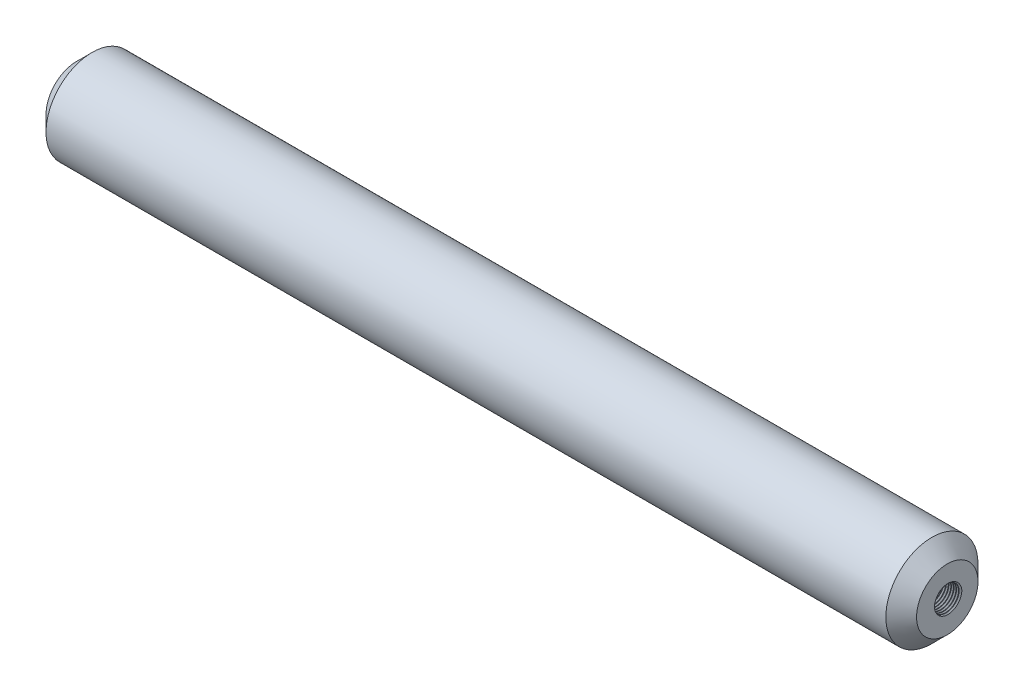
SolidWorks part; units mm, degrees
ref_plane "Front Plane" through (0, 0, 0) normal (0, 0, 1) x (1, 0, 0)
ref_plane "Top Plane" through (0, 0, 0) normal (0, 1, 0) x (1, 0, 0)
ref_plane "Right Plane" through (0, 0, 0) normal (1, 0, 0) x (0, 0, -1)
sketch "Sketch1" plane through (0, 0, 0) normal (1, 0, 0) x (0, 0, -1)
  circle A0 centre (0, 0) radius 9
  dimension "D1" = 18
extrude "Boss-Extrude1" add sketch "Sketch1" against normal blind 170
sketch "Sketch2" plane through (0, 0, 0) normal (1, 0, 0) x (0, 0, -1)
  circle A0 centre (0, 0) radius 2.5
  dimension "D1" = 5
extrude "Cut-Extrude1" cut sketch "Sketch2" against normal blind 24
sketch "Sketch3" plane through (-170, 0, 0) normal (-1, 0, 0) x (0, 0, 1)
  circle A0 centre (0, 0) radius 2.5
  dimension "D1" = 5
extrude "Cut-Extrude2" cut sketch "Sketch3" against normal blind 24
sketch "Sketch4" plane through (0, 0, 0) normal (1, 0, 0) x (0, 0, -1)
  circle A0 centre (0, 0) radius 2.5
  dimension "D1" = 5
curve "Helix/Spiral1" pitch 0.5 height 18 turns 36
sketch "Sketch5" plane through (0, 0, 0) normal (1, 0, 0) x (0, 0, -1)
  line L1 (2.5, 0) -> (0, 0) construction
  circle A0 centre (0, 0) radius 2.5 construction
sketch3d "3DSketch5"
  point P0 (0, 0, -2.5)
sketch3d "3DSketch6"
  line L0 (0.2, 0, -2.5) -> (-0.2, 0, -2.5)
  line L2 (0.2, 0, -2.5) -> (-0.0014, 0, -2.8472)
  line L3 (-0.0014, 0, -2.8472) -> (-0.2, 0, -2.5)
  point P11 (0, 0, -2.5)
  dimension "D1" = 0.4
  dimension "D2" = 0.4
sweep "Cut-Sweep5" cut profiles "3DSketch6" path "Helix/Spiral1"
sketch "Sketch8" plane through (-170, 0, 0) normal (-1, 0, 0) x (0, 0, 1)
  circle A0 centre (0, 0) radius 2.5
curve "Helix/Spiral3" pitch 0.5 height 18 turns 36
sketch "Sketch9" plane through (-170, 0, 0) normal (-1, 0, 0) x (0, 0, 1)
  line L0 (0, 0) -> (2.5, 0) construction
  circle A0 centre (0, 0) radius 2.5 construction
sketch3d "3DSketch7"
  point P0 (-170, 0, 2.5)
sketch3d "3DSketch8"
  line L0 (-169.8, 0, 2.5) -> (-170, 0, 2.8464)
  line L1 (-170.2, 0, 2.5) -> (-169.8, 0, 2.5)
  line L4 (-170, 0, 2.8464) -> (-170.2, 0, 2.5)
  point P0 (0, 0, 0)
  point P6 (-170, 0, 2.5)
  point P7 (-170, 0, 2.5)
  dimension "D1" = 0.4
  dimension "D2" = 0.4
  dimension "D3" = 0.4
sweep "Cut-Sweep6" cut profiles "3DSketch8" path "Helix/Spiral3"
chamfer "Chamfer1" distance 3 angle 45 2 edges at (-170, 0, -9) (0, 0, -9)
